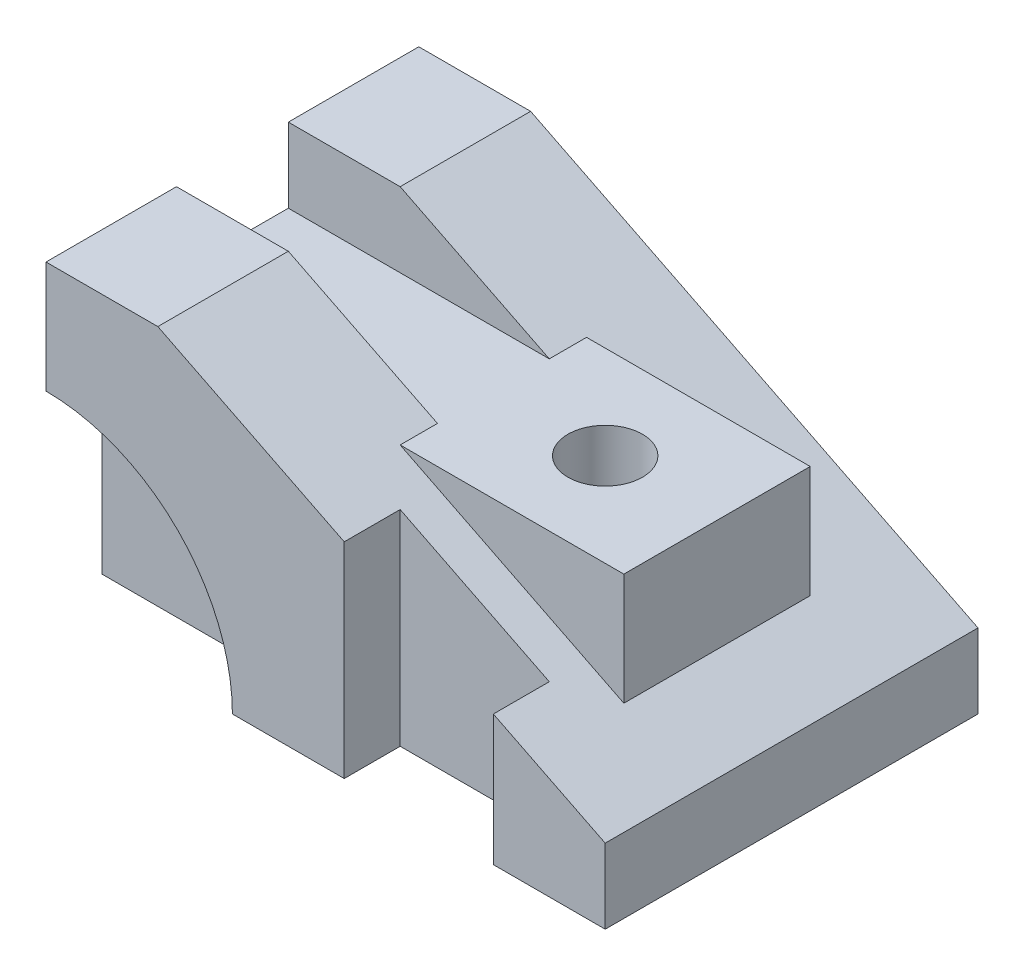
SolidWorks part; units mm, degrees
ref_plane "Front Plane" through (0, 0, 0) normal (0, 0, 1) x (1, 0, 0)
ref_plane "Top Plane" through (0, 0, 0) normal (0, 1, 0) x (1, 0, 0)
ref_plane "Right Plane" through (0, 0, 0) normal (1, 0, 0) x (0, 0, -1)
sketch "Sketch1" plane through (0, 0, 0) normal (0, 0, 1) x (1, 0, 0)
  line L0 (0, 0) -> (150, 0)
  line L1 (150, 0) -> (150, 20)
  line L2 (150, 20) -> (30, 80)
  line L3 (30, 80) -> (0, 80)
  line L4 (0, 80) -> (0, 0)
  dimension "D1" = 150
  dimension "D2" = 20
  dimension "D3" = 80
  dimension "D4" = 30
extrude "Boss-Extrude1" add sketch "Sketch1" against normal blind 50 and the other way blind 50
sketch "Sketch2" plane through (0, 0, 50) normal (0, 0, 1) x (1, 0, 0)
  circle A0 centre (0, 0) radius 50
  dimension "D1" = 100
extrude "Cut-Extrude1" cut sketch "Sketch2" against normal blind 15
sketch "Sketch3" plane through (0, 0, 0) normal (0, 0, 1) x (1, 0, 0)
  line L0 (70, 60) -> (130, 60)
  line L1 (150, 20) -> (30, 80) construction
  line L2 (130, 60) -> (130, 30)
  line L3 (130, 30) -> (70, 60)
  line L4 (150, 0) -> (150, 20) construction
  line L6 (30, 80) -> (0, 80) construction
  point P7 (150, 10)
  dimension "D1" = 20
  dimension "D2" = 30
  dimension "D3" = 20
extrude "Boss-Extrude2" add sketch "Sketch3" along normal blind 25 and the other way blind 25
sketch "Sketch4" plane through (0, 60, 0) normal (0, 1, 0) x (1, 0, 0)
  line L0 (-44, 0) -> (44, 0) construction
  line L2 (130, 25) -> (70, 25) construction
  line L3 (130, 25) -> (130, -25) construction
  circle A0 centre (100, 0) radius 10
  point P4 (0, 0)
  point P6 (0, 0)
  dimension "D1" = 20
  dimension "D2" = 30
  dimension "D3" = 25
extrude "Cut-Extrude2" cut sketch "Sketch4" against normal through all
sketch "Sketch5" plane through (0, 80, 0) normal (0, 1, 0) x (1, 0, 0)
  line L0 (-44, 0) -> (44, 0) construction
  line L1 (-50.1584, 15) -> (83.0747, 15)
  line L2 (-50.1584, 15) -> (-50.1584, -15)
  line L3 (-50.1584, -15) -> (83.0747, -15)
  line L4 (83.0747, 15) -> (83.0747, -15)
  dimension "D1" = 15
  dimension "D2" = 15
extrude "Cut-Extrude3" cut sketch "Sketch5" against normal blind 20
sketch "Sketch7" plane through (0, 0, 50) normal (0, 0, 1) x (1, 0, 0)
  line L0 (50, 0) -> (150, 0) construction
  line L1 (80, 0) -> (120, 0)
  line L2 (80, 0) -> (80, 80.773)
  line L3 (80, 80.773) -> (120, 80.773)
  line L4 (120, 0) -> (120, 80.773)
  line L5 (150, 0) -> (150, 20) construction
  dimension "D1" = 30
  dimension "D2" = 40
extrude "Cut-Extrude4" cut sketch "Sketch7" against normal blind 15
